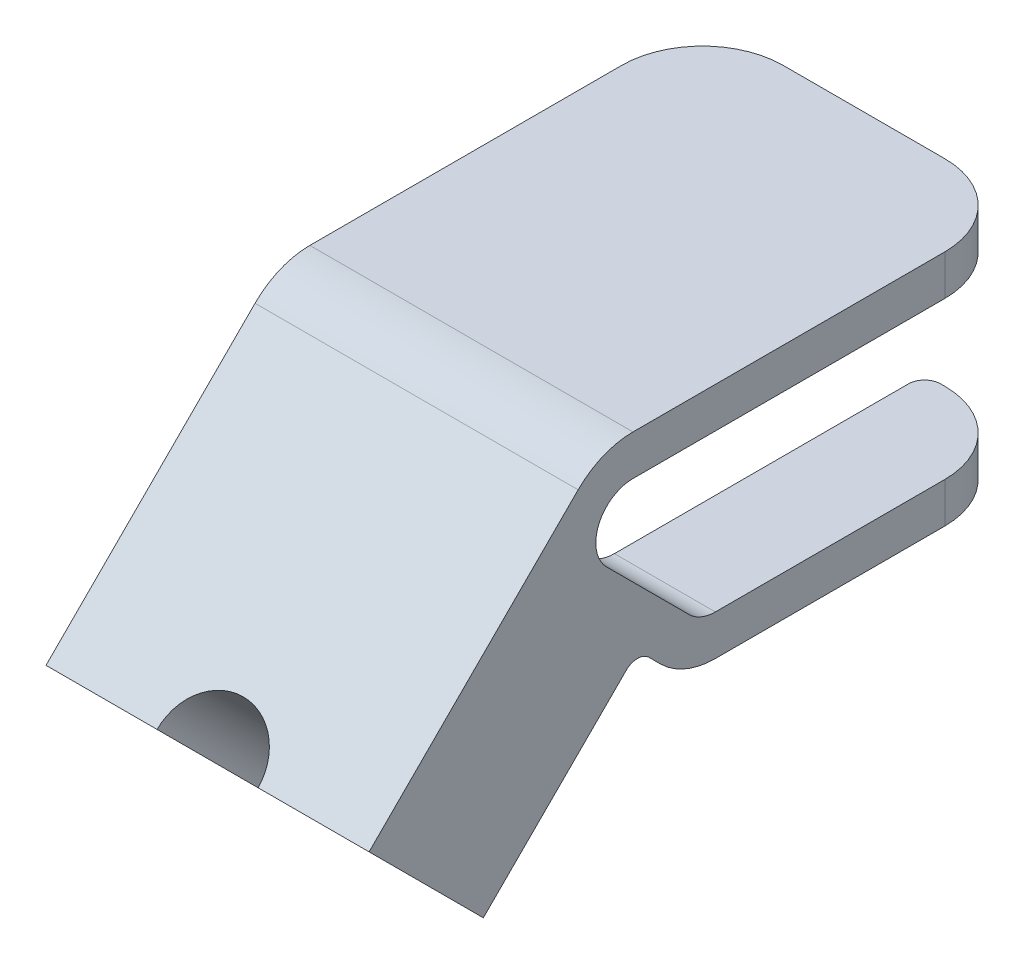
SolidWorks part; units mm, degrees
ref_plane "Front Plane" through (0, 0, 0) normal (0, 0, 1) x (1, 0, 0)
ref_plane "Top Plane" through (0, 0, 0) normal (0, 1, 0) x (1, 0, 0)
ref_plane "Right Plane" through (0, 0, 0) normal (1, 0, 0) x (0, 0, -1)
sketch "Sketch2" plane through (0, 0, 0) normal (1, 0, 0) x (0, 0, -1)
  line L0 (0, 0) -> (61.722, 0) construction
  line L1 (-3.9513, -9.5393) -> (9.0027, -22.4933) construction
  line L2 (12.954, -24.13) -> (61.722, -24.13) construction
  line L3 (61.722, 0) -> (61.722, -24.13) construction
  line L4 (0, 0.254) -> (61.722, 0.254)
  line L5 (-4.1309, -9.7189) -> (8.8231, -22.6729)
  line L6 (12.954, -24.384) -> (61.722, -24.384)
  line L7 (-4.1309, -9.7189) -> (-12.752, -1.0979) construction
  line L8 (-12.752, -1.0979) -> (-8.621, 3.033) construction
  arc A0 (0, 0) -> (-3.9513, -9.5393) centre (0, -5.588) ccw construction
  arc A1 (9.0027, -22.4933) -> (12.954, -24.13) centre (12.954, -18.542) ccw construction
  arc A2 (0, 0.254) -> (-4.1309, -9.7189) centre (0, -5.588) ccw
  arc A3 (8.8231, -22.6729) -> (12.954, -24.384) centre (12.954, -18.542) ccw
  circle A4 centre (0, -5.588) radius 12.192 construction
  point P11 (-8.3223, 4.0502)
  point P21 (-7.9506, 3.655)
  dimension "D1" = 67.31
  dimension "D3" = 5.588
  dimension "D5" = 5.588
  dimension "D8" = 6.35
  dimension "D2" = 45
  dimension "D4" = 24.13
  dimension "D6" = 0.254
extrude "Extrude-Thin1" add sketch "Sketch2" along normal mid plane 50.8 thin thin type one direction wall 6.35
sketch "Sketch3" plane through (0, 0, 0) normal (1, 0, 0) x (0, 0, -1)
  line L0 (7.9039, -30.734) -> (-15.446, -7.3841)
  line L1 (-15.446, -7.3841) -> (-4.8394, 3.2226)
  line L2 (-4.8394, 3.2226) -> (29.1171, -30.734)
  line L3 (29.1171, -30.734) -> (7.9039, -30.734)
  line L5 (12.954, -30.734) -> (61.722, -30.734) construction
  line L6 (-8.621, -14.209) -> (4.333, -27.163) construction
  line L8 (-12.752, -1.0979) -> (-8.621, 3.033) construction
  point P2 (-8.621, -14.209)
  point P10 (-23.0841, 0.254)
  point P12 (2.6651, -4.282)
  dimension "D1" = 15
  dimension "D2" = 2.54
extrude "Cut-Extrude1" cut sketch "Sketch3" against normal mid plane 19.05
ref_plane "Plane1" through (0, -1.0979, 12.752) normal (0, 0.7071, 0.7071) x (1, 0, 0)
sketch "Sketch4" plane through (0, -1.0979, 12.752) normal (0, 0.7071, 0.7071) x (1, 0, 0)
  line L0 (-7.9375, -40.6375) -> (-25.4, -40.6375)
  line L1 (-25.4, -40.6375) -> (-25.4, -6.35)
  line L2 (-25.4, -6.35) -> (-9.525, -6.35)
  line L3 (-9.525, -6.35) -> (-9.525, -1.6067) construction
  line L4 (-9.525, -6.35) -> (-9.525, -26.35)
  line L5 (-9.525, -26.35) -> (0, -26.35)
  line L6 (0, -26.35) -> (0, -32.7)
  line L8 (-9.525, 8.65) -> (9.525, 8.65) construction
  line L9 (-7.9375, -40.6375) -> (-7.9375, -26.35) construction
  arc A0 (0, -32.7) -> (-7.9375, -40.6375) centre (0, -40.6375) ccw
  dimension "D1" = 7.9375
  dimension "D2" = 35
  dimension "D3" = 6.35
extrude "Boss-Extrude1" add sketch "Sketch4" against normal blind 25.4
sketch "Sketch7" plane through (-25.4, 0, 0) normal (-1, 0, 0) x (0, 0, 1)
  line L0 (8.621, 3.033) -> (17.2421, -5.588)
  line L1 (17.2421, -5.588) -> (8.621, -14.209)
  line L2 (8.621, -14.209) -> (8.621, 3.033)
extrude "Boss-Extrude2" add sketch "Sketch7" against normal up to surface (15.875 mm away) up to face at (-9.525, -18.1537, 0.4125)
mirror "Mirror2" about plane through (0, 0, 0) normal (1, 0, 0) of "Boss-Extrude1", "Boss-Extrude2"
fillet "Fillet3" radius 2.54 2 edges at (17.4625, -23.5485, -0.7184) (-17.4625, -23.5485, -0.7184)
fillet "Fillet4" radius 12.7 4 edges at (25.4, 3.429, -61.722) (-25.4, 3.429, -61.722) (-25.4, -27.559, -61.722) (25.4, -27.559, -61.722)
sketch "Sketch6" plane through (0, -30.734, 0) normal (0, -1, 0) x (1, 0, 0)
  line L0 (12.7, -61.722) -> (-12.7, -61.722) construction
  line L1 (9.525, -12.954) -> (-9.525, -12.954)
  line L2 (9.525, -12.954) -> (9.525, -61.722)
  line L3 (9.525, -61.722) -> (-9.525, -61.722)
  line L4 (-9.525, -12.954) -> (-9.525, -61.722)
  point P7 (-2.8419, -12.954)
extrude "Cut-Extrude2" cut sketch "Sketch6" against normal up to next
fillet "Fillet6" radius 2.54 2 edges at (-9.525, -27.559, -61.722) (9.525, -27.559, -61.722)
sketch "Sketch8" plane through (0, 4.031, 4.031) normal (0, -0.7071, -0.7071) x (1, 0, 0)
  line L1 (9.525, 3.9513) -> (-9.525, 3.9513)
  line L2 (9.525, 3.9513) -> (9.525, 36.1433)
  line L3 (9.525, 36.1433) -> (-9.525, 36.1433)
  line L4 (-9.525, 3.9513) -> (-9.525, 36.1433)
  line L5 (9.525, 3.9513) -> (25.4, 3.9513) construction
  point P5 (0, 0)
extrude "Boss-Extrude3" add sketch "Sketch8" against normal up to surface (2.54 mm away) up to face at (0, -14.1047, 25.7588)
fillet "Fillet7" radius 5.08 4 edges at (9.525, 1.6213, 3.2382) (-9.525, 1.6213, 3.2382) (-9.525, -29.6084, 21.5059) (9.525, -29.6084, 21.5059)
